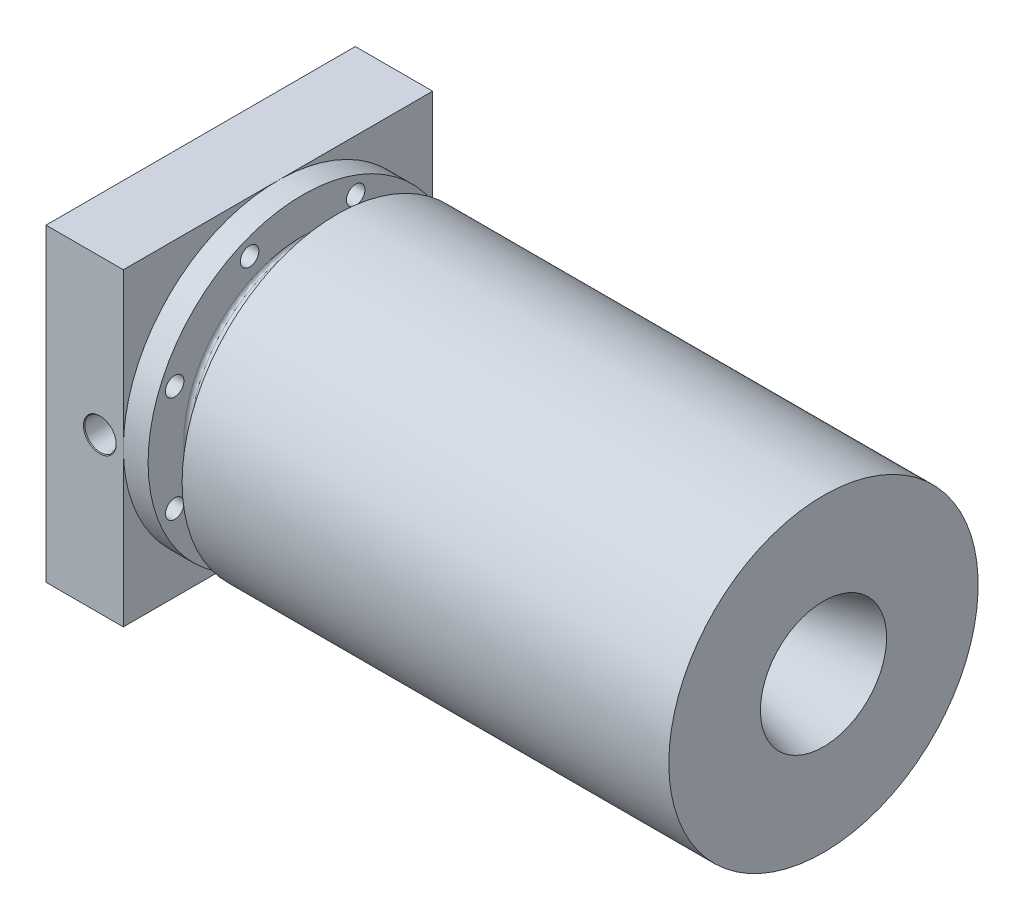
SolidWorks part; units mm, degrees
note: The reader was unsure of these and kept them because the rebuilt part matched: shared geometry of "Sketch2<2>".
other "Injector "
other "TC"
other "Volume " parameters "D11"=9.6936, "D1"=8.9273, "D2"=33.6348, "D3"=26.5468, "D4"=23.315, "D5"=33.6348, "D6"=5.8865, "D7"=63.1196, "D8"=7.0953, "D9"=1.4619, "D10"=3.7307, "D12"=6.1926, "D13"=4.361, "D14"=3.81, "D15"=11.3511, "D16"=3.7343, "D17"=3.7343, "D18"=7.0449
ref_plane "Front Plane" through (0, 0, 0) normal (0, 0, 1) x (1, 0, 0)
ref_plane "Top Plane" through (0, 0, 0) normal (0, 1, 0) x (1, 0, 0)
ref_plane "Right Plane" through (0, 0, 0) normal (1, 0, 0) x (0, 0, -1)
sketch "Chamber Revolve" plane through (0, 0, 0) normal (0, 0, 1) x (1, 0, 0)
  line L1 (223.9623, 63.5) -> (223.9623, 25.908)
  line L4 (189.463, 17.9788) -> (173.5582, 33.8836)
  line L5 (173.5582, 33.8836) -> (0, 33.8836)
  line L10 (0, 33.8836) -> (0, 42.5196)
  line L11 (0, 63.5) -> (10.16, 63.5)
  line L12 (10.16, 63.5) -> (10.16, 47.5996)
  line L13 (0, 0) -> (66.3921, 0) construction
  line L15 (191.9165, 17.3214) -> (223.9623, 25.908)
  line L16 (10.16, 47.5996) -> (24.13, 47.5996)
  line L17 (24.13, 47.5996) -> (24.13, 63.5)
  line L18 (24.13, 63.5) -> (223.9623, 63.5)
  line L19 (190.5, 16.9418) -> (191.9165, 17.3214) construction
  line L20 (190.5, 16.9418) -> (189.463, 17.9788) construction
  line L21 (0, 48.5902) -> (3.8608, 48.5902)
  line L22 (3.8608, 48.5902) -> (3.8608, 42.5196)
  line L23 (3.8608, 42.5196) -> (0, 42.5196)
  line L24 (0, 48.5902) -> (0, 63.5)
  arc A0 (189.463, 17.9788) -> (191.9165, 17.3214) centre (191.2591, 19.7748) ccw
  dimension "D11" = 2.54
  dimension "D2" = 67.7672
  dimension "D3" = 51.816
  dimension "D6" = 45
  dimension "D13" = 10.16
  dimension "D8" = 33.8836
  dimension "D9" = 33.4623
  dimension "D7" = 13.716
  dimension "D15" = 13.97
  dimension "D5" = 190.5
  dimension "D4" = 15
  dimension "D18" = 6.0706
  dimension "D12" = 127
revolve "Revolve1" add sketch "Chamber Revolve" angle 360 about L13
fillet "Fillet1" radius 1.27 2 edges at (24.13, 0, 47.5996) (10.16, 0, 47.5996)
sketch "Sketch2" plane through (0, 0, 0) normal (-1, 0, 0) x (0, 0, 1)
  line L0 (0, 0) -> (-24.2492, 58.6875) construction
  line L1 (0, 0) -> (0, 56.6825) construction
  circle A0 centre (-21.7273, 52.584) radius 3.81
  circle A1 centre (0, 0) radius 63.5 construction
  dimension "D2" = 7.62
  dimension "D1" = 6.604
  dimension "D3" = 22.45
extrude "Cut-Extrude1" cut sketch "Sketch2" against normal up to next
pattern_circular "CirPattern1" count 8 over 360 about axis through (0, 0, 0) along (1, 0, 0) of "Cut-Extrude1"
sketch "Sketch4" plane through (0, 0, 0) normal (-1, 0, 0) x (0, 0, 1)
  circle A0 centre (0, 0) radius 63.5
  circle A1 centre (0, 0) radius 63.5 construction
extrude "Boss-Extrude1" add sketch "Sketch4" along normal blind 31.75 separate body
sketch "Sketch5" plane through (0, 0, 0) normal (1, 0, 0) x (0, 0, -1)
  circle A0 centre (21.7273, 52.584) radius 3.81 construction
  circle A1 centre (21.7273, 52.584) radius 3.81
extrude "Cut-Extrude6" cut sketch "Sketch2<2>" along normal through all
sketch "Sketch2<2>" plane through (0, 0, 0) normal (-1, 0, 0) x (0, 0, 1) same geometry as "Sketch2"
pattern_circular "CirPattern2" count 8 over 360 about axis through (0, 0, 0) along (1, 0, 0) of "Cut-Extrude6"
sketch "Sketch11" plane through (-31.75, 0, 0) normal (-1, 0, 0) x (0, 0, 1)
  line L1 (-63.5, -63.5) -> (63.5, -63.5)
  line L2 (-63.5, -63.5) -> (-63.5, 63.5)
  line L3 (-63.5, 63.5) -> (63.5, 63.5)
  line L4 (63.5, -63.5) -> (63.5, 63.5)
  circle A0 centre (0, 0) radius 63.5 construction
  circle A1 centre (0, 0) radius 63.5
  point P6 (0, 63.5)
  point P9 (-63.5, 0)
  circle M18 centre (0, 0) radius 63.5
  dimension "D1" = 127
extrude "Boss-Extrude2" add sketch "Sketch11" against normal up to surface (31.75 mm away) contours L3 L2 L1 M18 | L1 L4 L3 M18 | L4 L3 M18 | L2 L1 M18
sketch "Sketch12" plane through (0, 0, 0) normal (1, 0, 0) x (0, 0, -1)
  circle A0 centre (0, 0) radius 24.13
  dimension "D1" = 48.26
extrude "Cut-Extrude4" cut sketch "Sketch12" against normal blind 15.24
sketch "Sketch13" plane through (0, 0, 63.5) normal (0, 0, 1) x (1, 0, 0)
  line L1 (0, 63.5) -> (0, -63.5) construction
  line L2 (70.5417, 0) -> (-70.5417, 0) construction
  circle A0 centre (-9.652, 0) radius 1.905
  dimension "D1" = 3.81
  dimension "D2" = 9.652
extrude "Cut-Extrude5" cut sketch "Sketch13" against normal up to next and the other way through all
sketch "Sketch14" plane through (0, 0, 0) normal (1, 0, 0) x (0, 0, -1)
  line L0 (-63.5, 63.5) -> (63.5, 63.5) construction
  line L1 (-63.5, -63.5) -> (63.5, -63.5) construction
  line L2 (-12.7, 63.5) -> (-63.5, 63.5)
  line L3 (-63.5, 63.5) -> (-63.5, -63.5)
  line L4 (-63.5, -63.5) -> (-12.7, -63.5)
  arc A0 (-12.7, 63.5) -> (-12.7, -63.5) centre (0, 0) ccw
  circle A1 centre (0, 0) radius 63.5 construction
  dimension "D1" = 12.7
sketch "Sketch15" plane through (-31.75, 0, 0) normal (-1, 0, 0) x (0, 0, 1)
  point P0 (0, 0)
hole_wizard "1/4 NPT Tapped Hole2" positions "Sketch15" profile "Sketch17" size "1/4" standard "ANSI Inch" end condition up to next
cosmetic thread "Hole Thread1" parameters "D1"=19.05, "D2"=14.2562
sketch "Sketch17" plane through (-31.75, 0, 0) normal (0, 1, 0) x (0, 0, 1)
  line L0 (0, 0) -> (0, 16.511)
  line L1 (0, 16.511) -> (5.5626, 16.511)
  line L3 (5.5626, 16.511) -> (5.5626, 19.05)
  line L4 (5.5626, 19.05) -> (5.9502, 19.05)
  line L5 (5.9502, 19.05) -> (6.5141, 0.2169)
  line L6 (6.5141, 0.2169) -> (6.731, 0)
  line L7 (6.731, 0) -> (0, 0)
  line L8 (0, -6.35) -> (0, 107.95) construction
  line L9 (-6.5141, 0.2169) -> (-6.731, 0) construction
  line L11 (-5.5626, 19.05) -> (-5.9502, 19.05) construction
  line L12 (-5.9502, 19.05) -> (-6.5141, 0.2169) construction
  dimension "Thru Tap Drill Dia." = 11.1252
  dimension "Thru Tap Drill Depth" = 16.511
  dimension "Thread Dia." = 13.0281
  dimension "Thread Angle" = 3.43
  dimension "Thread Depth" = 19.05
  dimension "Near C'Sink Dia." = 13.462
  dimension "Near C'Sink Angle" = 90
chamfer "Chamfer1" distance 4.572 angle 45 1 edges at (0, 0, -24.13)
sketch "Sketch18" plane through (0, 0, 63.5) normal (0, 0, 1) x (1, 0, 0)
  point P0 (-9.652, 0)
hole_wizard "1/4 NPT Tapped Hole1" positions "Sketch18" profile "Sketch20" size "1/4" standard "ANSI Inch"
sketch "Sketch20" plane through (-9.652, 0, 63.5) normal (1, 0, 0) x (0, -1, 0)
  line L0 (0, 0) -> (0, 26.9643)
  line L1 (5.5626, 23.622) -> (0, 26.9643)
  line L2 (-5.5626, 23.622) -> (0, 26.9643) construction
  line L3 (5.5626, 23.622) -> (5.5626, 16.51)
  line L4 (5.5626, 16.51) -> (5.9525, 16.51)
  line L5 (5.9525, 16.51) -> (6.438, 0.293)
  line L6 (6.438, 0.293) -> (6.731, 0)
  line L7 (6.731, 0) -> (0, 0)
  line L8 (0, -6.35) -> (0, 107.95) construction
  line L9 (-6.438, 0.293) -> (-6.731, 0) construction
  line L11 (-5.5626, 16.51) -> (-5.9525, 16.51) construction
  line L12 (-5.9525, 16.51) -> (-6.438, 0.293) construction
  dimension "Tap Drill Dia." = 11.1252
  dimension "Tap Drill Depth" = 23.622
  dimension "Thread Dia." = 12.876
  dimension "Thread Angle" = 3.43
  dimension "Thread Depth" = 16.51
  dimension "C'Sink Dia." = 13.462
  dimension "C'Sink Angle" = 90
  dimension "Drill Angle" = 118
cosmetic thread "Hole Thread2" parameters "D1"=16.51, "D2"=14.1041
mirror "Mirror1" about plane through (0, 0, 0) normal (0, 0, 1) of "1/4 NPT Tapped Hole1", "Cut-Extrude5"
cosmetic thread "Hole Thread3" parameters "D1"=16.51, "D2"=14.1041
sketch "Sketch21" plane through (0, 0, 0) normal (0, 1, 0) x (1, 0, 0)
  line L0 (0, 33.8836) -> (173.5582, 33.8836)
  line L1 (0, 42.5196) -> (0, -42.5196) construction
  line L2 (0, 33.8836) -> (0, -33.8836) construction
  line L3 (173.5582, -33.8836) -> (173.5582, 33.8836) construction
  line L4 (173.5582, 33.8836) -> (189.463, 17.9788)
  line L5 (189.463, -17.9788) -> (189.463, 17.9788) construction
  line L6 (189.463, 17.9788) -> (189.463, 0)
  line L10 (0, 0) -> (0, 33.8836)
  line L11 (0, 0) -> (189.463, 0)
  line L12 (189.463, 0) -> (214.4295, 0) construction
revolve "Revolve2" add sketch "Sketch21" angle 360 about L12
fillet "Fillet2" radius 0.889 2 edges at (3.8608, 0, 42.5196) (3.8608, 0, 48.5902)
sketch "Sketch22" plane through (-31.75, 0, 0) normal (-1, 0, 0) x (0, 0, 1)
  point P0 (0, -33.02)
  point P6 (0, -28.5755)
  dimension "D1" = 33.02
hole_wizard "1/4-28 Tapped Hole1" positions "Sketch22" profile "Sketch23" tap size "1/4-28" standard "ANSI Inch"
sketch "Sketch23" plane through (-31.75, -33.02, 0) normal (0, 1, 0) x (0, 0, 1)
  line L0 (0, 0) -> (0, 18.3894)
  line L1 (0, 18.3894) -> (2.7051, 16.764)
  line L2 (2.7051, 16.764) -> (2.7051, 1.1049)
  line L3 (2.7051, 1.1049) -> (3.81, 0)
  line L5 (3.81, 0) -> (0, 0)
  line L6 (-2.7051, 1.1049) -> (-3.81, 0) construction
  line L10 (0, 18.3894) -> (-2.7051, 16.764) construction
  line L11 (0, -6.35) -> (0, 107.95) construction
  dimension "Tap Drill Dia." = 5.4102
  dimension "Tap Drill Depth" = 16.764
  dimension "Near C'Sink Dia." = 7.62
  dimension "Near C'Sink Angle" = 90
  dimension "Drill Angle" = 118
cosmetic thread "Hole Thread4" parameters "D1"=13.97, "D2"=6.35
mirror "Mirror2" about plane through (0, 0, 0) normal (0, 1, 0) of "1/4-28 Tapped Hole1"
cosmetic thread "Hole Thread5" parameters "D1"=13.97
equation "\"Throat Diameter\"= 1.334"
equation "\"Exit Diameter\"= 2.04"
equation "\"D3@Chamber Revolve\"=\"Exit Diameter\""
equation "\"D8@Chamber Revolve\"=\"Throat Diameter\""
equation "\"Injector Ox D\"= 3mm"
equation "\"Injector Fuel D\"= 2mm"
equation "\"Chamber Diameter\"= \"Chamber Throat D Ratio\" * ( \"Throat Diameter\" )"
equation "\"Chamber Throat D Ratio\"= 2"
equation "\"L*\"= 30"
equation "\"Lc\"= \"L*\" / ( \"Chamber Throat D Ratio\" ^ 2 )"
equation "\"T_min\"= 2 * .17"
equation "\"D2@Chamber Revolve\"=\"Chamber Diameter\""
equation "\"D7@Chamber Revolve\"=\"T_min\" +.2"
equation "\"D5@Chamber Revolve\"=\"Lc\""
equation "\"No Flange Holes\"= 8"
equation "\"D1@CirPattern1\"=\"No Flange Holes\""
equation "\"D16@Chamber Revolve\"=\"T_min\""
